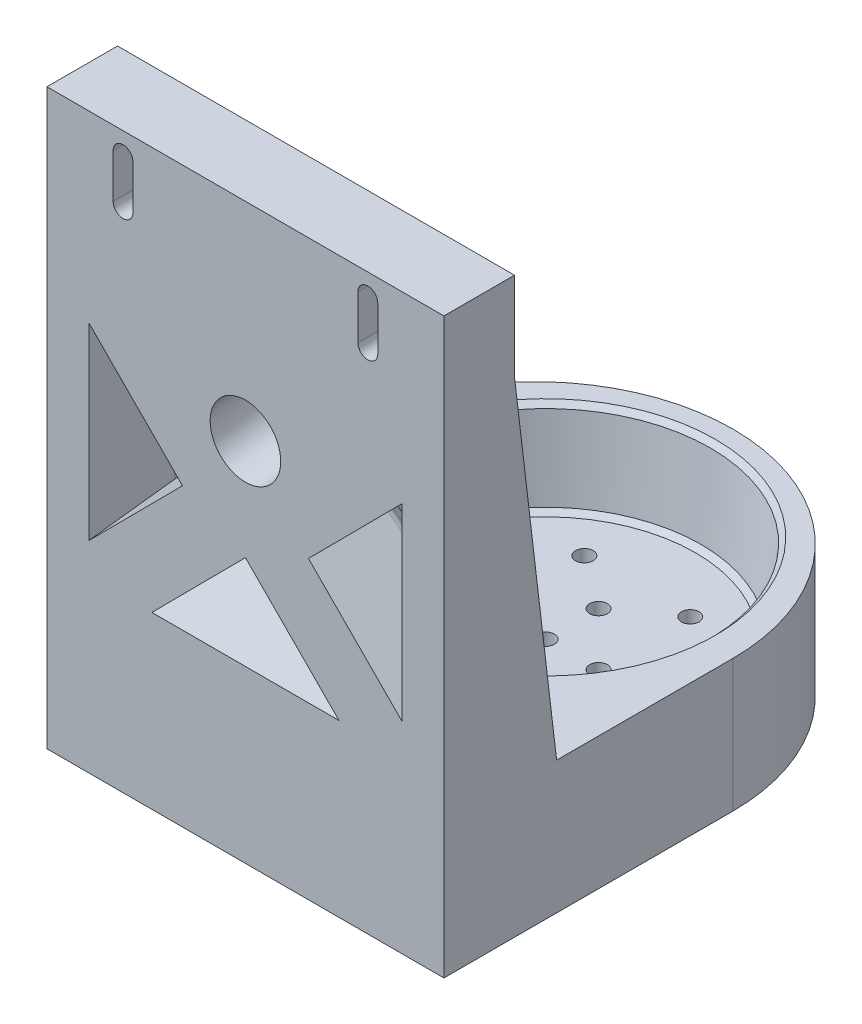
SolidWorks part; units mm, degrees
ref_plane "Front Plane" through (0, 0, 0) normal (0, 0, 1) x (1, 0, 0)
ref_plane "Top Plane" through (0, 0, 0) normal (0, 1, 0) x (1, 0, 0)
ref_plane "Right Plane" through (0, 0, 0) normal (1, 0, 0) x (0, 0, -1)
sketch "Sketch1" plane through (0, 0, 0) normal (1, 0, 0) x (0, 0, -1)
  line L0 (0, 0) -> (85, 0)
  line L2 (-9.5536, 100) -> (-25.5536, 100)
  line L3 (-25.5536, 100) -> (-25.5536, -30)
  line L4 (85, 0) -> (85, -30)
  line L5 (85, -30) -> (-25.5536, -30)
  line L7 (0, 0) -> (-9.5536, 80)
  line L8 (-9.5536, 80) -> (-9.5536, 100)
  point P5 (-7.3187, 100)
  dimension "D1" = 96.81
  dimension "D2" = 85
  dimension "D3" = 130
  dimension "D4" = 16
  dimension "D5" = 30
  dimension "D6" = 20
extrude "Boss-Extrude1" add sketch "Sketch1" along normal blind 90
sketch "Sketch2" plane through (0, 0, 9.5536) normal (0, 0, -1) x (-1, 0, 0)
  line L0 (-72.75, 95) -> (-72.75, 85) construction
  line L1 (-70.5, 95) -> (-70.5, 85)
  line L2 (-75, 95) -> (-75, 85)
  line L3 (-45, 100) -> (-45, 80) construction
  line L4 (-90, 100) -> (0, 100) construction
  line L5 (-90, 80) -> (0, 80) construction
  line L6 (-90, 80) -> (-90, 100) construction
  line L7 (-17.25, 95) -> (-17.25, 85) construction
  line L8 (-19.5, 95) -> (-19.5, 85)
  line L9 (-15, 95) -> (-15, 85)
  arc A0 (-70.5, 95) -> (-75, 95) centre (-72.75, 95) ccw
  arc A1 (-75, 85) -> (-70.5, 85) centre (-72.75, 85) ccw
  arc A2 (-19.5, 95) -> (-15, 95) centre (-17.25, 95) cw
  arc A3 (-15, 85) -> (-19.5, 85) centre (-17.25, 85) cw
  point P2 (-72.75, 90)
  point P17 (-17.25, 90)
  point P22 (0, 0)
  point P23 (0, 0)
  point P24 (0, 0)
  dimension "D1" = 5
  dimension "D2" = 15
  dimension "D3" = 4.5
  dimension "D4" = 10
extrude "Cut-Extrude1" cut sketch "Sketch2" against normal through all
sketch "Sketch4" plane through (0, 0, 0) normal (0, 1, 0) x (1, 0, 0)
  line L0 (45, 85) -> (45, 0) construction
  line L1 (90, 85) -> (0, 85) construction
  line L2 (90, 0) -> (0, 0) construction
  circle A0 centre (45, 42.5) radius 37.5
  dimension "D1" = 75
extrude "Cut-Extrude2" cut sketch "Sketch4" against normal blind 20 draft 6.81
sketch "Sketch5" plane through (0, 0, 0) normal (0, 0.1186, -0.9929) x (-1, 0, 0)
  line L0 (-45, 80.5684) -> (-45, 0) construction
  line L1 (-90, 80.5684) -> (0, 80.5684) construction
  line L2 (-90, 0) -> (0, 0) construction
  circle A0 centre (-45, 55.5684) radius 8
  point P8 (0, 0)
  point P9 (0, 0)
  dimension "D1" = 16
  dimension "D2" = 25
extrude "Cut-Extrude3" cut sketch "Sketch5" against normal through all
sketch "Sketch6" plane through (0, 0, 0) normal (0, 0.1186, -0.9929) x (-1, 0, 0)
  line L0 (-45, 80.5684) -> (-45, 0) construction
  line L1 (-90, 80.5684) -> (0, 80.5684) construction
  line L2 (-90, 0) -> (0, 0) construction
  circle A0 centre (-45, 55.5684) radius 10
  dimension "D1" = 20
extrude "Cut-Extrude4" cut sketch "Sketch6" against normal blind 2
fillet "Fillet1" radius 45 2 edges at (0, -15, -85) (90, -15, -85)
sketch "Sketch7" plane through (0, 0, 0) normal (0, 0.1186, -0.9929) x (-1, 0, 0)
  line L0 (-45, 80.5684) -> (-45, 0) construction
  line L1 (-90, 80.5684) -> (0, 80.5684) construction
  line L2 (-90, 0) -> (0, 0) construction
  line L3 (-45, 32.8533) -> (-66.2132, 11.6401)
  line L4 (-66.2132, 11.6401) -> (-23.7868, 11.6401)
  line L5 (-23.7868, 11.6401) -> (-45, 32.8533)
  line L6 (-80.494, 18.5724) -> (-59.2808, 39.7856)
  line L7 (-59.2808, 39.7856) -> (-80.494, 60.9988)
  line L8 (-80.494, 60.9988) -> (-80.494, 18.5724)
  line L9 (-30.7192, 39.7856) -> (-9.506, 60.9988)
  line L10 (-9.506, 18.5724) -> (-30.7192, 39.7856)
  line L11 (-9.506, 60.9988) -> (-9.506, 18.5724)
  point P11 (-55.6066, 22.2467)
  dimension "D1" = 30
  dimension "D2" = 30
  dimension "D3" = 30
  dimension "D4" = 30
  dimension "D5" = 15
extrude "Cut-Extrude5" cut sketch "Sketch7" against normal through all
chamfer "Chamfer1" distance 3 angle 45 9 edges at (45, 11.5579, 1.3802) (55.6066, 22.0897, 2.6379) (34.3934, 22.0897, 2.6379) (20.1126, 28.9732, 3.46) (9.506, 39.5049, 4.7177) (20.1126, 50.0367, 5.9754) (69.8874, 28.9732, 3.46) (80.494, 39.5049, 4.7177) (69.8874, 50.0367, 5.9754)
chamfer "Chamfer2" distance 1 angle 45 2 edges at (45, -20, -7.3884) (45, 0, -5) first distance on face at (45, -20, -7.3884) first distance on face at (45, 0, -5)
fillet "Fillet3" radius 2 9 edges at (80.494, 39.1492, 7.6965) (69.8874, 49.681, 8.9542) (69.8874, 28.6174, 6.4388) (45, 11.2022, 4.3591) (55.6066, 21.734, 5.6168) (34.3934, 21.734, 5.6168) (20.1126, 28.6174, 6.4388) (20.1126, 49.681, 8.9542) (9.506, 39.1492, 7.6965)
sketch "Sketch8" plane through (0, -20, 0) normal (0, 1, 0) x (1, 0, 0)
  line L0 (45, 76.4679) -> (45, 8.5321) construction
  line L1 (11.0321, 42.5) -> (78.9679, 42.5) construction
  circle A0 centre (45, 42.5) radius 33.9679 construction
  circle A1 centre (45, 42.5) radius 2
  circle A2 centre (45, 54.5) radius 2
  circle A3 centre (21, 42.5) radius 2
  circle A4 centre (57, 42.5) radius 2
  circle A5 centre (45, 30.5) radius 2
  circle A6 centre (33, 42.5) radius 2
  circle A7 centre (33, 63.2846) radius 2
  circle A8 centre (57, 63.2846) radius 2
  circle A9 centre (69, 42.5) radius 2
  circle A10 centre (57, 21.7154) radius 2
  circle A11 centre (33, 21.7154) radius 2
  point P21 (45, 42.5)
  point P32 (45, 42.5)
  dimension "D1" = 4
  dimension "D2" = 12
  dimension "D3" = 24
  dimension "D4" = 4
  dimension "D5" = 6
extrude "Cut-Extrude6" cut sketch "Sketch8" along direction (0, 1, 0) on the side against the normal through all
